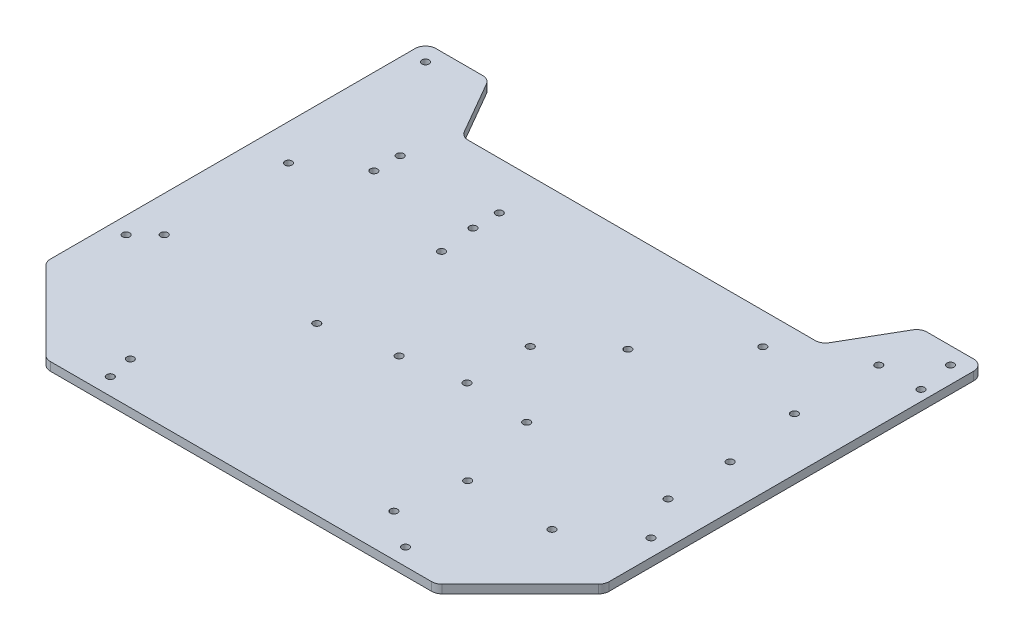
SolidWorks part; units mm, degrees
material "Acier non allié"
ref_plane "Front" through (0, 0, 0) normal (0, 0, 1) x (1, 0, 0)
ref_plane "Top" through (0, 0, 0) normal (0, 1, 0) x (1, 0, 0)
ref_plane "Right" through (0, 0, 0) normal (1, 0, 0) x (0, 0, -1)
sketch "Main scetch" plane through (0, 0, 0) normal (0, 1, 0) x (1, 0, 0)
  line L1 (0, 0) -> (132.5, 0) construction
  line L2 (0, 0) -> (0, 220) construction
  line L3 (0, 220) -> (132.5, 220) construction
  line L4 (132.5, 0) -> (132.5, 220) construction
  line L13 (-92.5, 0) -> (92.5, 0)
  line L14 (92.5, 0) -> (132.5, 40)
  line L15 (132.5, 40) -> (132.5, 220)
  line L16 (132.5, 220) -> (102.5, 220)
  line L17 (102.5, 220) -> (85.1795, 190)
  line L18 (85.1795, 190) -> (-85.1795, 190)
  line L19 (-102.5, 220) -> (-85.1795, 190)
  line L20 (-132.5, 220) -> (-102.5, 220)
  line L21 (-132.5, 40) -> (-132.5, 220)
  line L22 (-92.5, 0) -> (-132.5, 40)
  point P11 (0, 190)
  dimension "132.5" = 132.5
  dimension "D2" = 220
  dimension "D1" = 40
  dimension "D3" = 40
  dimension "D4" = 30
  dimension "D5" = 60
  dimension "D6" = 30
extrude "Main extrusion" add sketch "Main scetch" along normal blind 4
fillet "Congé1" radius 5 10 edges at (-132.5, 2, -40) (-92.5, 2, 0) (92.5, 2, 0) (132.5, 2, -40) (132.5, 2, -220) (102.5, 2, -220) (85.1795, 2, -190) (-85.1795, 2, -190) (-102.5, 2, -220) (-132.5, 2, -220)
sketch "Esquisse1" plane through (0, 4, 0) normal (0, 1, 0) x (1, 0, 0)
  line L0 (0, 0) -> (0, 218.5516) construction
  line L1 (132.5, 42.0711) -> (132.5, 215) construction
  line L2 (127.5, 220) -> (105.3868, 220) construction
  line L3 (-90.4289, 0) -> (90.4289, 0) construction
  circle A0 centre (70, 8) radius 1
  circle A1 centre (124.5, 70) radius 1
  circle A2 centre (124.5, 212) radius 1
  circle A3 centre (-124.5, 212) radius 1
  circle A4 centre (-124.5, 70) radius 1
  circle A5 centre (-70, 8) radius 1
  dimension "D1" = 2
  dimension "D2" = 2
  dimension "D3" = 2
  dimension "D4" = 8
  dimension "D5" = 8
  dimension "D6" = 8
  dimension "D7" = 8
  dimension "D8" = 70
  dimension "D9" = 70
extrude "Enlèv. mat.-Extru.1" cut sketch "Esquisse1" against normal through all
hole_wizard "Dégagement M31" positions "Esquisse2" profile "Esquisse3" hole size "M3" standard "ISO" end condition through all
sketch "Esquisse2" plane through (0, 4, 0) normal (0, 1, 0) x (1, 0, 0)
  point P0 (-124.5, 212)
  point P3 (-124.5, 70)
  point P6 (-70, 8)
  point P9 (70, 8)
  point P12 (124.5, 70)
  point P15 (124.5, 212)
sketch "Esquisse3" plane through (-124.5, 4, -212) normal (1, 0, 0) x (0, 0, 1)
  line L0 (0, 0) -> (0, 4)
  line L1 (0, 4) -> (1.7, 4)
  line L2 (1.7, 4) -> (1.7, 0)
  line L5 (1.7, 0) -> (0, 0)
  line L11 (0, -6.35) -> (0, 107.95) construction
  dimension "Diamètre du perçage jusqu'au prochain" = 3.4
  dimension "Profondeur du perçage jusqu'au prochain" = 4
sketch "Esquisse4" plane through (0, 4, 0) normal (0, 1, 0) x (1, 0, 0)
  line L0 (-132.5, 215) -> (-132.5, 42.0711) construction
  line L2 (82.2927, 190) -> (-82.2927, 190) construction
  line L3 (132.5, 42.0711) -> (132.5, 215) construction
  line L4 (-90.4289, 0) -> (90.4289, 0) construction
  line L5 (127.5, 220) -> (105.3868, 220) construction
  circle A1 centre (-68.5, 185) radius 1 construction
  circle A5 centre (72.5, 175) radius 1
  circle A6 centre (41.5, 142) radius 1
  circle A7 centre (107.5, 155) radius 1
  circle A8 centre (127.5, 195) radius 1
  circle A9 centre (112, 120) radius 1
  circle A10 centre (112.5, 90) radius 1
  circle A11 centre (17.2, 120) radius 1
  circle A12 centre (17.2, 90) radius 1
  circle A13 centre (47.5, 88) radius 1
  circle A14 centre (57.5, 50) radius 1
  circle A15 centre (97.5, 50) radius 1
  circle A16 centre (52.5, 20) radius 1
  circle A17 centre (-10, 85) radius 1
  circle A18 centre (-72.5, 20) radius 1
  circle A19 centre (107.5, 195) radius 1
  circle A23 centre (-115.5, 138) radius 1
  circle A24 centre (-42.86, 138) radius 1
  circle A25 centre (-115.5, 79.07) radius 1
  circle A26 centre (-42.8904, 78.82) radius 1
  circle A27 centre (-92, 167.5) radius 1
  circle A28 centre (-45, 167.5) radius 1
  circle A29 centre (-92, 155) radius 1
  circle A30 centre (-45, 155) radius 1
  dimension "D4" = 2
  dimension "D13" = 2
  dimension "D16" = 2
  dimension "D19" = 2
  dimension "D24" = 2
  dimension "D25" = 2
  dimension "D28" = 2
  dimension "D30" = 2
  dimension "D32" = 2
  dimension "D36" = 2
  dimension "D37" = 2
  dimension "D40" = 2
  dimension "D48" = 2
  dimension "D49" = 2
  dimension "D50" = 2
  dimension "D52" = 2
  dimension "D11" = 2
  dimension "D12" = 2
  dimension "D65" = 2
  dimension "D66" = 2
  dimension "D58" = 2
  dimension "D61" = 2
  dimension "D70" = 2
  dimension "D71" = 2
  dimension "D14" = 205
  dimension "D15" = 15
  dimension "D20" = 25
  dimension "D21" = 65
  dimension "D22" = 5
  dimension "D23" = 25
  dimension "D26" = 20.5
  dimension "D27" = 100
  dimension "D29" = 30
  dimension "D31" = 115.3
  dimension "D33" = 115.3
  dimension "D34" = 132
  dimension "D35" = 85
  dimension "D38" = 50
  dimension "D39" = 75
  dimension "D41" = 35
  dimension "D42" = 80
  dimension "D43" = 20
  dimension "D44" = 20
  dimension "D45" = 205
  dimension "D46" = 85
  dimension "D47" = 142.5
  dimension "D51" = 25
  dimension "D53" = 25
  dimension "D54" = 5
  dimension "D55" = 64
  dimension "D7" = 59.18
  dimension "D8" = 72.64
  dimension "D9" = 58.93
  dimension "D10" = 72.61
  dimension "D67" = 17
  dimension "D68" = 138
  dimension "D56" = 23.5
  dimension "D57" = 23.5
  dimension "D59" = 17.5
  dimension "D60" = 17.5
  dimension "D62" = 12.5
  dimension "D63" = 12.5
  dimension "D64" = 23.5
  dimension "D69" = 23.5
  dimension "D17" = 33
  dimension "D18" = 31
extrude "Enlèv. mat.-Extru.2" cut sketch "Esquisse4" against normal through all
hole_wizard "Dégagement M32" positions "Esquisse5" profile "Esquisse6" hole size "M3" standard "ISO" end condition through all
sketch "Esquisse5" plane through (0, 4, 0) normal (0, 1, 0) x (1, 0, 0)
  point P9 (17.2, 120)
  point P18 (41.5, 142)
  point P21 (72.5, 175)
  point P24 (107.5, 155)
  point P27 (127.5, 195)
  point P30 (112, 120)
  point P33 (112.5, 90)
  point P36 (47.5, 88)
  point P39 (17.2, 90)
  point P42 (57.5, 50)
  point P45 (97.5, 50)
  point P48 (-10, 85)
  point P51 (-72.5, 20)
  point P54 (52.5, 20)
  point P57 (107.5, 195)
  point P86 (-115.5, 138)
  point P89 (-42.86, 138)
  point P92 (-115.5, 79.07)
  point P95 (-42.8904, 78.82)
  point P102 (-92, 167.5)
  point P105 (-92, 155)
  point P108 (-45, 155)
  point P111 (-45, 167.5)
sketch "Esquisse6" plane through (17.2, 4, -120) normal (1, 0, 0) x (0, 0, 1)
  line L0 (0, 0) -> (0, 4)
  line L1 (0, 4) -> (1.7, 4)
  line L2 (1.7, 4) -> (1.7, 0)
  line L5 (1.7, 0) -> (0, 0)
  line L11 (0, -6.35) -> (0, 107.95) construction
  dimension "Diamètre du perçage jusqu'au prochain" = 3.4
  dimension "Profondeur du perçage jusqu'au prochain" = 4
equation "\"WIDTH\"= 300mm'Total width of the robot"
equation "\"LENGTH\"= 220mm'Total length of the robot"
equation "\"D2@Main scetch\" = \"LENGTH\""
equation "\"CUT_DEPTH\"= 45mm'Depth of the cut on the edges of the plate"
equation "\"Plate_th\"= 3mm'Thickness of the plate"
equation "\"D1\"= \"Plate_th\""
equation "\"D47@Esquisse4\"=(80+205)/2"
